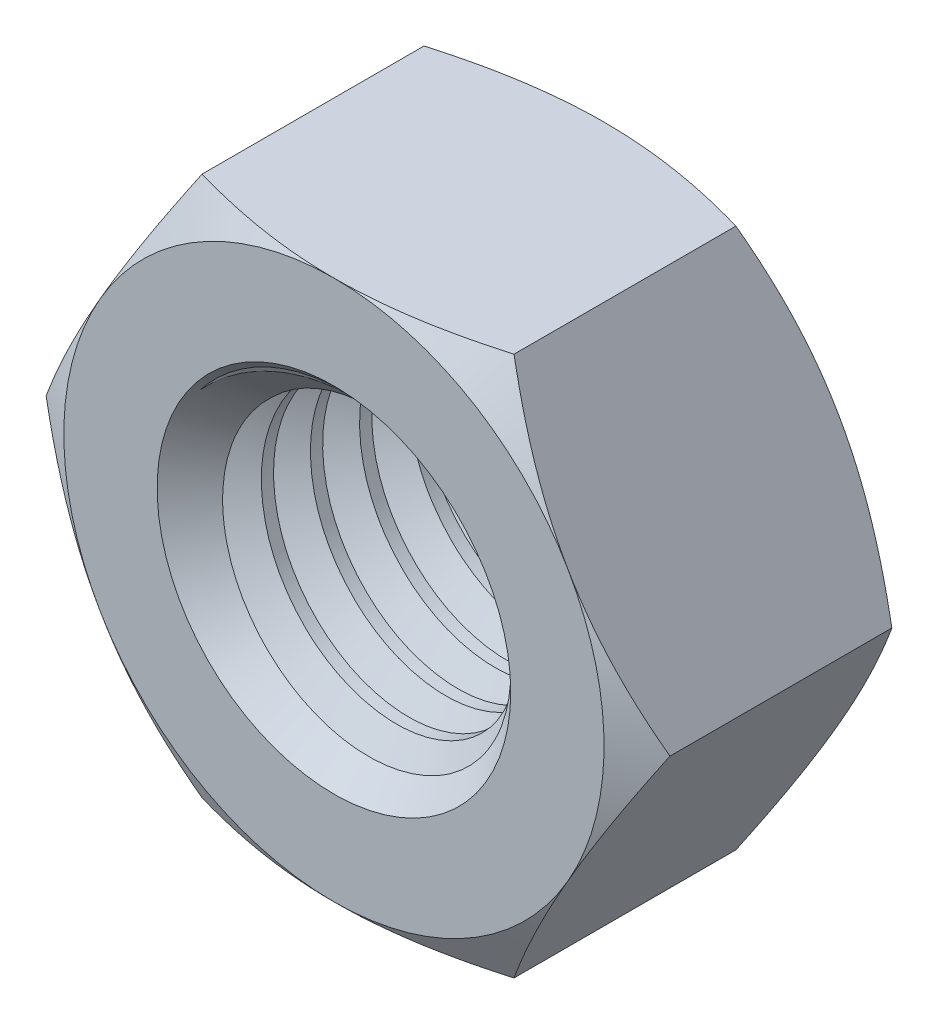
SolidWorks part; units mm, degrees
ref_plane "Front" through (0, 0, 0) normal (0, 0, 1) x (1, 0, 0)
ref_plane "Top" through (0, 0, 0) normal (0, 1, 0) x (1, 0, 0)
ref_plane "Right" through (0, 0, 0) normal (1, 0, 0) x (0, 0, -1)
sketch "Çizim1" plane through (0, 0, 0) normal (0, 0, 1) x (1, 0, 0)
  line L1 (12.7017, 0) -> (6.3509, 11)
  line L2 (6.3509, 11) -> (-6.3509, 11)
  line L3 (-6.3509, 11) -> (-12.7017, 0)
  line L4 (-12.7017, 0) -> (-6.3509, -11)
  line L5 (-6.3509, -11) -> (6.3509, -11)
  line L6 (6.3509, -11) -> (12.7017, 0)
  circle A0 centre (0, 0) radius 11 construction
  point P1 (0, 0)
  point P10 (0, 0)
  dimension "D1" = 22
extrude "Yükseklik-Ekstrüzyon1" add sketch "Çizim1" along normal blind 11
sketch "Çizim2" plane through (0, 0, 11) normal (0, 0, 1) x (1, 0, 0)
  circle A0 centre (0, 0) radius 11
extrude "Kes-Ekstrüzyon1" cut sketch "Çizim2" against normal blind 11 draft 60 flip side to cut
sketch "Çizim3" plane through (0, 0, 0) normal (0, 0, -1) x (-1, 0, 0)
  circle A0 centre (0, 0) radius 11
extrude "Kes-Ekstrüzyon2" cut sketch "Çizim3" against normal blind 11 draft 60 flip side to cut
sketch "Çizim4" plane through (0, 0, 0) normal (0, 0, -1) x (-1, 0, 0)
  circle A0 centre (0, 0) radius 5.7
  dimension "D1" = 11.4
extrude "Kes-Ekstrüzyon3" cut sketch "Çizim4" against normal blind 11
chamfer "Pah1" distance 1.5 angle 45 2 edges at (-5.7, 0, 11) (-5.7, 0, 0)
sketch "Çizim6" plane through (0, 0, 11) normal (0, 0, 1) x (1, 0, 0)
  circle A0 centre (0, 0) radius 5.7
curve "Helis/Spiral1" pitch 2 height 13 radius 5.7 centre (0, 0, 11) axis (0, 0, -1) start towards (-1, 0, 0)
ref_plane "Düzlem1" through (5.7, 0, -2) normal (0, -0.9984, -0.0558) x (-1, 0, 0)
sketch "Çizim7" plane through (5.7, 0, -2) normal (0, -0.9984, -0.0558) x (-1, 0, 0)
  line L1 (-1.3, 0) -> (0.3652, -0.9614)
  line L3 (0.3652, 0.9614) -> (-1.3, 0)
  line L5 (0.65, 0) -> (0.65, 1.1258) [skipped]
  line L6 (0.3652, 0.9614) -> (0.3652, -0.9614)
  circle A0 centre (0, 0) radius 0.65 construction
  dimension "D1" = 1.3
sweep "Kes-Süpür1" cut profiles "Çizim7" path "Helis/Spiral1" align with end faces yes
